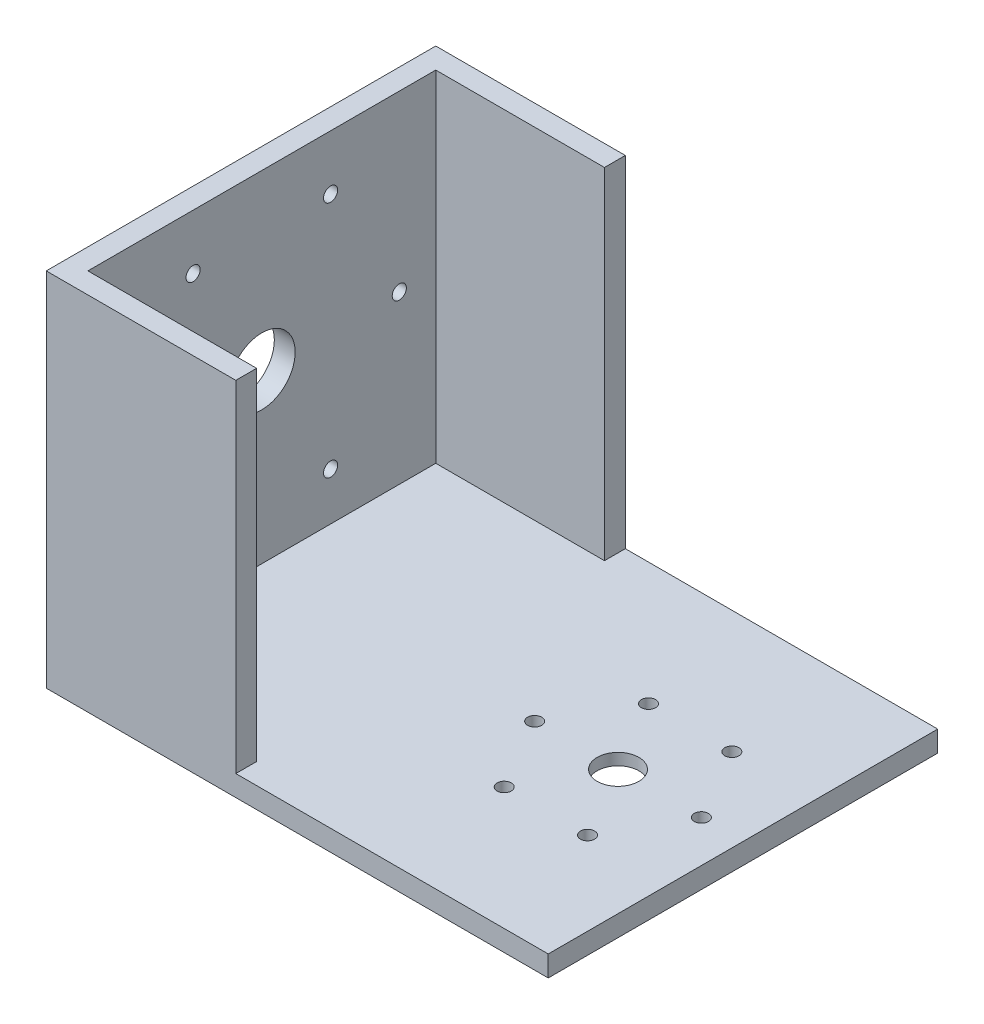
SolidWorks part; units mm, degrees
material "6061-T6 (SS)"
ref_plane "Front Plane" through (0, 0, 0) normal (0, 0, 1) x (1, 0, 0)
ref_plane "Top Plane" through (0, 0, 0) normal (0, 1, 0) x (1, 0, 0)
ref_plane "Right Plane" through (0, 0, 0) normal (1, 0, 0) x (0, 0, -1)
sketch "SK_Output_Plate" plane through (0, 0, 0) normal (0, 1, 0) x (1, 0, 0)
  line L0 (-90.5, 46.75) -> (30, 46.75)
  line L1 (30, 46.75) -> (30, -46.75)
  line L2 (30, -46.75) -> (-90.5, -46.75)
  line L3 (-90.5, -46.75) -> (-90.5, 46.75)
  circle A0 centre (20, 0) radius 1.7
  circle A1 centre (10, 17.3205) radius 1.7
  circle A2 centre (-10, 17.3205) radius 1.7
  circle A3 centre (-20, 0) radius 1.7
  circle A4 centre (-10, -17.3205) radius 1.7
  circle A5 centre (10, -17.3205) radius 1.7
  circle A6 centre (0, 0) radius 5
  dimension "D9_SK_Output_Plate" = 3.4
  dimension "D11_SK_Output_Plate" = 3.4
  dimension "D14_SK_Output_Plate" = 3.4
  dimension "D17_SK_Output_Plate" = 3.4
  dimension "D19_SK_Output_Plate" = 3.4
  dimension "D22_SK_Output_Plate" = 3.4
  dimension "D25_SK_Output_Plate" = 10
  dimension "P1" = 90.5
  dimension "P2" = 46.75
  dimension "P3" = 30
  dimension "P4" = 46.75
  dimension "P5" = 30
  dimension "P6" = 46.75
  dimension "P7" = 90.5
  dimension "P8" = 46.75
  dimension "P10" = 20
  dimension "P12" = 10
  dimension "P13" = 17.3205
  dimension "P15" = 10
  dimension "P16" = 17.3205
  dimension "P18" = 20
  dimension "P20" = 10
  dimension "P21" = 17.3205
  dimension "P23" = 10
  dimension "P24" = 17.3205
extrude "Output_Plate" add sketch "SK_Output_Plate" along normal blind 5
sketch "SK_Pitch_Pilot_Recess" plane through (0, 0, 0) normal (0, 1, 0) x (1, 0, 0)
  circle A0 centre (0, 0) radius 15.15
  dimension "D1_SK_Pitch_Pilot_Recess" = 30.3
extrude "Pitch_Pilot_Recess" cut sketch "SK_Pitch_Pilot_Recess" along normal blind 2.2
ref_plane "PL_Rear_Plate_base" through (-90.5, 0, 0) normal (1, 0, 0) x (0, 0, -1)
sketch "SK_Rear_Plate" plane through (-90.5, 0, 0) normal (1, 0, 0) x (0, 0, -1)
  line L0 (46.75, 0) -> (46.75, 86.75)
  line L1 (46.75, 86.75) -> (-46.75, 86.75)
  line L2 (-46.75, 86.75) -> (-46.75, 0)
  line L3 (-46.75, 0) -> (46.75, 0)
  circle A0 centre (0, 45) radius 8
  circle A1 centre (33, 45) radius 1.7
  circle A2 centre (16.5, 73.5788) radius 1.7
  circle A3 centre (-16.5, 73.5788) radius 1.7
  circle A4 centre (-33, 45) radius 1.7
  circle A5 centre (-16.5, 16.4212) radius 1.7
  circle A6 centre (16.5, 16.4212) radius 1.7
  dimension "D7_SK_Rear_Plate" = 16
  dimension "D9_SK_Rear_Plate" = 3.4
  dimension "D12_SK_Rear_Plate" = 3.4
  dimension "D15_SK_Rear_Plate" = 3.4
  dimension "D18_SK_Rear_Plate" = 3.4
  dimension "D21_SK_Rear_Plate" = 3.4
  dimension "D24_SK_Rear_Plate" = 3.4
  dimension "P1" = 46.75
  dimension "P2" = 46.75
  dimension "P3" = 86.75
  dimension "P4" = 46.75
  dimension "P5" = 86.75
  dimension "P6" = 46.75
  dimension "P8" = 45
  dimension "P10" = 33
  dimension "P11" = 45
  dimension "P13" = 16.5
  dimension "P14" = 73.5788
  dimension "P16" = 16.5
  dimension "P17" = 73.5788
  dimension "P19" = 33
  dimension "P20" = 45
  dimension "P22" = 16.5
  dimension "P23" = 16.4212
  dimension "P25" = 16.5
  dimension "P26" = 16.4212
extrude "Rear_Plate" add sketch "SK_Rear_Plate" along normal blind 5
ref_plane "PL_Top_Plate_base" through (0, 0, 41.75) normal (0, 0, 1) x (1, 0, 0)
sketch "SK_Top_Plate" plane through (0, 0, 41.75) normal (0, 0, 1) x (1, 0, 0)
  line L0 (-90.5, 0) -> (-45, 0)
  line L1 (-45, 0) -> (-45, 86.75)
  line L2 (-45, 86.75) -> (-90.5, 86.75)
  line L3 (-90.5, 86.75) -> (-90.5, 0)
  dimension "P1" = 90.5
  dimension "P2" = 45
  dimension "P3" = 45
  dimension "P4" = 86.75
  dimension "P5" = 90.5
  dimension "P6" = 86.75
extrude "Top_Plate" add sketch "SK_Top_Plate" along normal blind 5
ref_plane "PL_Bottom_Plate_base" through (0, 0, -46.75) normal (0, 0, 1) x (1, 0, 0)
sketch "SK_Bottom_Plate" plane through (0, 0, -46.75) normal (0, 0, 1) x (1, 0, 0)
  line L0 (-90.5, 0) -> (-45, 0)
  line L1 (-45, 0) -> (-45, 86.75)
  line L2 (-45, 86.75) -> (-90.5, 86.75)
  line L3 (-90.5, 86.75) -> (-90.5, 0)
  dimension "P1" = 90.5
  dimension "P2" = 45
  dimension "P3" = 45
  dimension "P4" = 86.75
  dimension "P5" = 90.5
  dimension "P6" = 86.75
extrude "Bottom_Plate" add sketch "SK_Bottom_Plate" along normal blind 5
equation "\"Roll_axis_y\"= 45"
equation "\"Roll_rear_x\"= -85.5"
